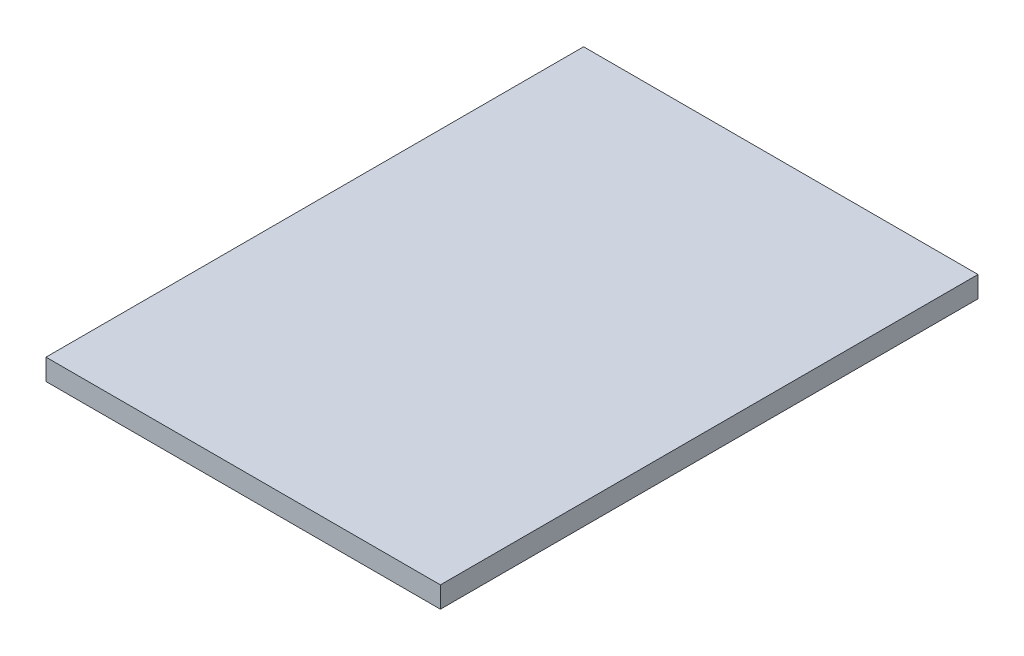
SolidWorks part; units mm, degrees
material "Perspex (TM) GS Acrylic Cast Sheet"
ref_plane "Front Plane" through (0, 0, 0) normal (0, 0, 1) x (1, 0, 0)
ref_plane "Top Plane" through (0, 0, 0) normal (0, 1, 0) x (1, 0, 0)
ref_plane "Right Plane" through (0, 0, 0) normal (1, 0, 0) x (0, 0, -1)
sketch "Sketch1" plane through (0, 0, 0) normal (0, 1, 0) x (1, 0, 0)
  line L1 (-84, -114.5) -> (84, -114.5)
  line L2 (-84, -114.5) -> (-84, 114.5)
  line L3 (-84, 114.5) -> (84, 114.5)
  line L4 (84, -114.5) -> (84, 114.5)
  line L5 (-84, -114.5) -> (84, 114.5) construction
  line L6 (-84, 114.5) -> (84, -114.5) construction
  point P0 (0, 0)
  dimension "D1" = 168
  dimension "D2" = 229
extrude "Boss-Extrude1" add sketch "Sketch1" along normal blind 9
sketch "Sketch2" plane through (0, 9, 0) normal (0, 1, 0) x (1, 0, 0)
  line L14 (-75, -105.5) -> (75, -105.5)
  line L15 (75, -105.5) -> (75, 105.5)
  line L16 (75, 105.5) -> (-75, 105.5)
  line L17 (-75, 105.5) -> (-75, -105.5)
  line L18 (-75, -105.5) -> (75, -105.5)
  line L19 (75, -105.5) -> (75, 105.5)
  line L20 (75, 105.5) -> (-75, 105.5)
  line L21 (-75, 105.5) -> (-75, -105.5)
  dimension "D1" = 9
equation "\"PCLength\"= 150mm'Length across I/O from PS to GPU"
equation "\"PCWidth\"= 340mm'Distance of longest part parallel to GPU(ussually GPU)"
equation "\"PCHeight\"= 190mm'Tallest point with mobo laying flat"
equation "\"WallThickness\"= 9mm'Thickness of each outer tank wall"
equation "\"ThermoBarrierThickness\"= 6mm'Thickness of barrier between hot side and cold side"
equation "\"HotSideGap\"= 15mm'Space in the hot side that hot fluid flows into"
equation "\"PCClearance\"= 40mm'Clearance from top of tank to top of PC"
equation "\"RadiatorHeight\"= 277.37mm'Final Height from ground of radiators"
equation "\"AirflowGap\"= 26mm'Distance between radiators and tank for airflow"
equation "\"VolumeSubtraction\"= 230mm"
equation "\"D1@Sketch1\"=\"PCLength\" + (2 * \"WallThickness\")"
equation "\"D1@Boss-Extrude1\"=\"WallThickness\""
equation "\"D2@Sketch1\"=\"PCHeight\" + \"ThermoBarrierThickness\" + \"HotSideGap\" + (2 * \"WallThickness\")"
